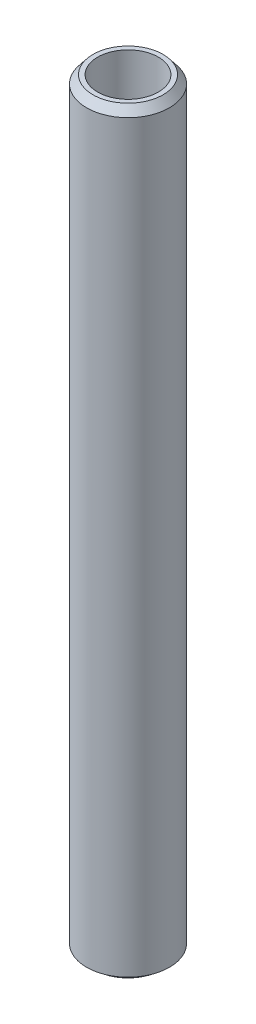
SolidWorks part; units mm, degrees
ref_plane "Front Plane" through (0, 0, 0) normal (0, 0, 1) x (1, 0, 0)
ref_plane "Top Plane" through (0, 0, 0) normal (0, 1, 0) x (1, 0, 0)
ref_plane "Right Plane" through (0, 0, 0) normal (1, 0, 0) x (0, 0, -1)
sketch "Sketch1" plane through (0, 0, 0) normal (0, 1, 0) x (1, 0, 0)
  circle A0 centre (0, 0) radius 20
  dimension "SHAFT_OD" = 40
extrude "Boss-Extrude1" add sketch "Sketch1" along normal blind 366.3215
sketch "Sketch2" plane through (0, 0, 0) normal (0, 1, 0) x (1, 0, 0)
  circle A0 centre (0, 0) radius 14.6532
  dimension "BORE_D" = 29.3063
extrude "Cut-Extrude1" cut sketch "Sketch2" along normal through all
chamfer "Chamfer1" distance 3.8912 angle 38.372 2 edges at (0, 366.3215, 20) (0, 0, 20) first distance on face at (0, 366.3215, 20) first distance on face at (0, 0, 14.6532)
